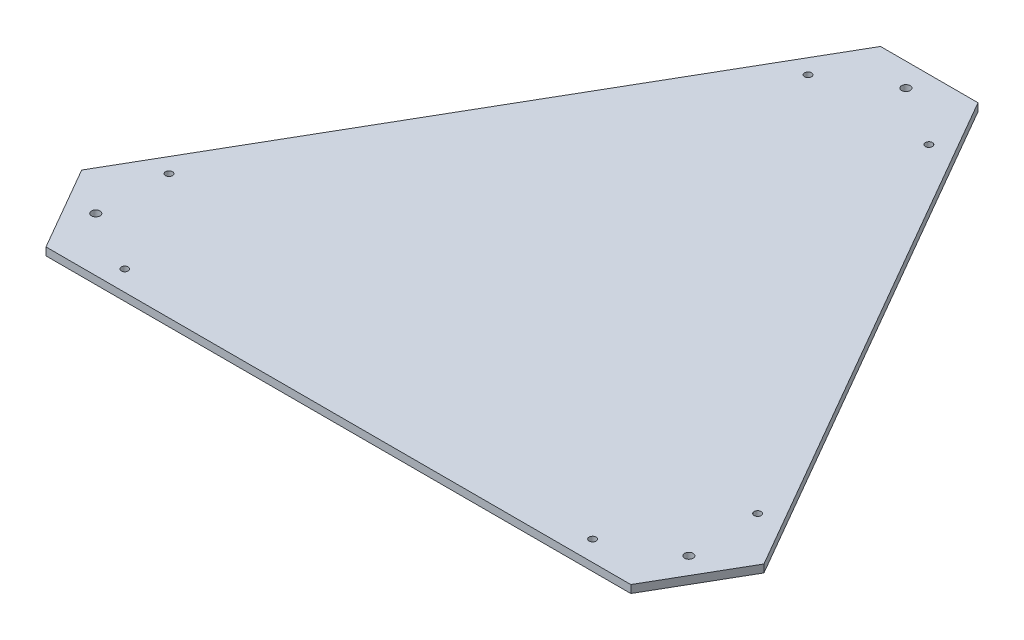
SolidWorks part; units mm, degrees
ref_plane "Plan de face" through (0, 0, 0) normal (0, 0, 1) x (1, 0, 0)
ref_plane "Plan de dessus" through (0, 0, 0) normal (0, 1, 0) x (1, 0, 0)
ref_plane "Plan de droite" through (0, 0, 0) normal (1, 0, 0) x (0, 0, -1)
sketch "Esquisse1" plane through (0, 0, 0) normal (0, 1, 0) x (1, 0, 0)
  line L0 (-31.25, 234.5485) -> (31.25, 234.5485)
  line L1 (31.25, 234.5485) -> (218.75, -90.211)
  line L2 (218.75, -90.211) -> (187.5, -144.3376)
  line L3 (187.5, -144.3376) -> (-187.5, -144.3376)
  line L4 (-187.5, -144.3376) -> (-218.75, -90.211)
  line L5 (-218.75, -90.211) -> (-31.25, 234.5485)
  line L6 (0, 234.5485) -> (0, 0) construction
  line L7 (0, 0) -> (203.125, -117.2743) construction
  line L8 (-203.125, -117.2743) -> (0, 0) construction
  line L9 (-125, 72.1688) -> (0, 0) construction
  line L10 (0, 0) -> (0, -144.3376) construction
  line L11 (125, 72.1688) -> (0, 0) construction
  line L12 (-31.25, 234.5485) -> (0, 288.6751) construction
  line L13 (0, 288.6751) -> (31.25, 234.5485) construction
  line L14 (-218.75, -90.211) -> (-250, -144.3376) construction
  line L15 (-250, -144.3376) -> (-187.5, -144.3376) construction
  dimension "D1" = 500
  dimension "D2" = 120
  dimension "D3" = 375
extrude "Boss.-Extru.1" add sketch "Esquisse1" along normal blind 5
ref_plane "Plan1" through (-15.625, 0, 27.0633) normal (-0.5, 0, 0.866) x (0, -1, 0)
ref_plane "Plan2" through (15.625, 0, -27.0633) normal (-0.5, 0, 0.866) x (0, -1, 0)
ref_plane "Plan3" through (0, 0, 0) normal (-0.5, 0, 0.866) x (0.866, 0, 0.5)
sketch "Esquisse2" plane through (0, 5, 0) normal (0, 1, 0) x (1, 0, 0)
  line L0 (-190.1346, -109.7743) -> (0, 0) construction
  line L1 (0, 0) -> (0, 219.5485) construction
  line L2 (0, 0) -> (190.1346, -109.7743) construction
  line L3 (31.25, 234.5485) -> (-31.25, 234.5485) construction
  circle A0 centre (0, 219.5485) radius 2.75
  circle A1 centre (-190.1346, -109.7743) radius 2.75
  circle A2 centre (190.1346, -109.7743) radius 2.75
  dimension "D1" = 5.5
  dimension "D2" = 120
  dimension "D3" = 120
  dimension "D4" = 15
  dimension "D5" = 219.5485
  dimension "D6" = 219.5485
extrude "Enlèv. mat.-Extru.1" cut sketch "Esquisse2" against normal up to next
ref_plane "Plan4" through (15.625, 0, 27.0633) normal (-0.5, 0, -0.866) x (0, -1, 0)
ref_plane "Plan5" through (-15.625, 0, -27.0633) normal (-0.5, 0, -0.866) x (0, -1, 0)
ref_plane "Plan6" through (0, 0, 0) normal (-0.5, 0, -0.866) x (-0.866, 0, 0.5)
sketch "Esquisse3" [suppressed] plane through (0, 6, 0) normal (0, 1, 0) x (1, 0, 0)
  line L0 (31.25, 234.5485) -> (-31.25, 234.5485) construction
  line L3 (0, 209.5485) -> (0, 0) construction
  line L4 (-10, 234.5485) -> (10, 234.5485)
  line L5 (-10, 234.5485) -> (-10, 209.5485)
  line L6 (-10, 209.5485) -> (10, 209.5485)
  line L7 (10, 234.5485) -> (10, 209.5485)
  dimension "D1" = 20
  dimension "D2" = 25
extrude "Enlèv. mat.-Extru.2" [suppressed] cut sketch "Esquisse3" against normal up to next
ref_axis "Axe1" through (0, -0.25, 0) along (0, 1, 0)
sketch "Esquisse5" [suppressed] plane through (0, 6, 0) normal (0, 1, 0) x (1, 0, 0)
  line L1 (-10, 209.5485) -> (10, 209.5485) construction
  circle A0 centre (0, 188.5485) radius 11.5
  dimension "D2" = 23
  dimension "D1" = 34
extrude "Enlèv. mat.-Extru.3" [suppressed] cut sketch "Esquisse5" against normal blind 21
pattern_circular "Répétition circulaire1" [suppressed] count 3 every 120 about axis through (0, -0.25, 0) along (0, 1, 0) of bodies 105
sketch "Esquisse6" plane through (0, 5, 0) normal (0, 1, 0) x (1, 0, 0)
  line L0 (-150, -131.3376) -> (150, -131.3376) construction
  line L1 (0, 0) -> (0, -131.3376) construction
  line L2 (-187.5, -144.3376) -> (187.5, -144.3376) construction
  circle A0 centre (-150, -131.3376) radius 2.25
  circle A1 centre (150, -131.3376) radius 2.25
  dimension "D1" = 4.5
  dimension "D2" = 13
  dimension "D3" = 300
extrude "Enlèv. mat.-Extru.4" cut sketch "Esquisse6" against normal up to next
pattern_circular "Répétition circulaire2" count 3 over 360 about axis through (0, -0.25, 0) along (0, 1, 0) of "Enlèv. mat.-Extru.4"
equation "\"epaisseu\"=5"
equation "\"D1@Boss.-Extru.1\"=\"epaisseu\""
